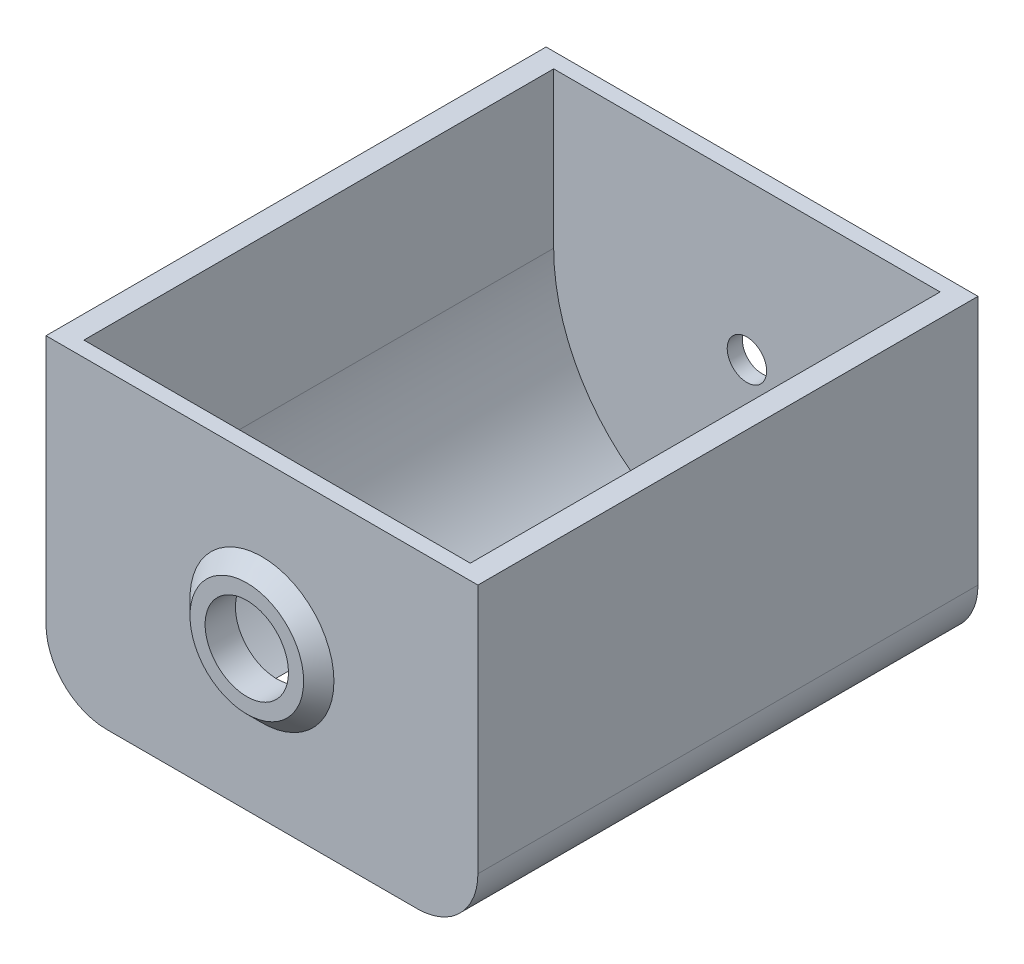
SolidWorks part; units mm, degrees
ref_plane "Piano frontale" through (0, 0, 0) normal (0, 0, 1) x (1, 0, 0)
ref_plane "Piano superiore" through (0, 0, 0) normal (0, 1, 0) x (1, 0, 0)
ref_plane "Piano destro" through (0, 0, 0) normal (1, 0, 0) x (0, 0, -1)
sketch "Schizzo1" plane through (0, 0, 0) normal (0, 0, 1) x (1, 0, 0)
  line L0 (-25.5, -25.5) -> (-25.5, 25.5) construction
  line L1 (0, 25.5) -> (0, -25.5) construction
  line L2 (-28.5, -20.5) -> (-28.5, 20.5)
  line L3 (-28.5, 25.5) -> (0, 25.5) construction
  line L4 (-28.5, 20.5) -> (-25.5, 20.5)
  line L5 (-28.5, -25.5) -> (-28.5, 25.5) construction
  line L6 (-28.5, -25.5) -> (0, -25.5) construction
  line L7 (-28.5, -20.5) -> (-15.1658, -20.5)
  line L8 (28.5, 20.5) -> (25.5, 20.5)
  line L9 (28.5, -20.5) -> (28.5, 20.5)
  line L10 (28.5, -20.5) -> (15.1658, -20.5)
  line L11 (-28.5, -20.5) -> (0, -20.5) construction
  line L12 (-28.5, 20.5) -> (0, 20.5) construction
  line L13 (-25.5, 0) -> (-25.5, 20.5)
  line L14 (25.5, 0) -> (25.5, 20.5)
  arc A0 (-25.5, 0) -> (-15.1658, -20.5) centre (0, 0) ccw
  arc A1 (15.1658, -20.5) -> (25.5, 0) centre (0, 0) ccw
  point P6 (-25.5, 0)
  point P9 (25.5, 0)
  dimension "D1" = 51
  dimension "D2" = 3
  dimension "D3" = 5
  dimension "D4" = 5
extrude "Estrusione-Estrusione1" add sketch "Schizzo1" along normal blind 62
sketch "Schizzo2" plane through (0, 0, 62) normal (0, 0, 1) x (1, 0, 0)
  line L1 (-28.5, 20.5) -> (28.5, 20.5)
  line L2 (-28.5, 20.5) -> (-28.5, -20.5)
  line L3 (-28.5, -20.5) -> (28.5, -20.5)
  line L4 (28.5, 20.5) -> (28.5, -20.5)
  circle A0 centre (0, 0) radius 5.5
  dimension "D1" = 11
extrude "Estrusione-Estrusione2" add sketch "Schizzo2" along normal blind 2
sketch "Schizzo3" plane through (0, 0, 64) normal (0, 0, 1) x (1, 0, 0)
  circle A0 centre (0, 0) radius 5.5
  circle A1 centre (0, 0) radius 7.5
  dimension "D1" = 2
extrude "Estrusione-Estrusione3" add sketch "Schizzo3" along normal blind 2
chamfer "Smusso1" distance 2 angle 45 1 edges at (7.5, 0, 64)
sketch "Schizzo4" plane through (0, 0, 0) normal (0, 0, -1) x (-1, 0, 0)
  line L1 (-28.5, 20.5) -> (28.5, 20.5)
  line L2 (-28.5, 20.5) -> (-28.5, -20.5)
  line L3 (-28.5, -20.5) -> (28.5, -20.5)
  line L4 (28.5, 20.5) -> (28.5, -20.5)
  circle A0 centre (0, 0) radius 2.6
  dimension "D1" = 5.2
extrude "Estrusione-Estrusione4" add sketch "Schizzo4" along normal blind 2
fillet "Raccordo1" radius 8 2 edges at (-28.5, -20.5, 31) (28.5, -20.5, 31)
